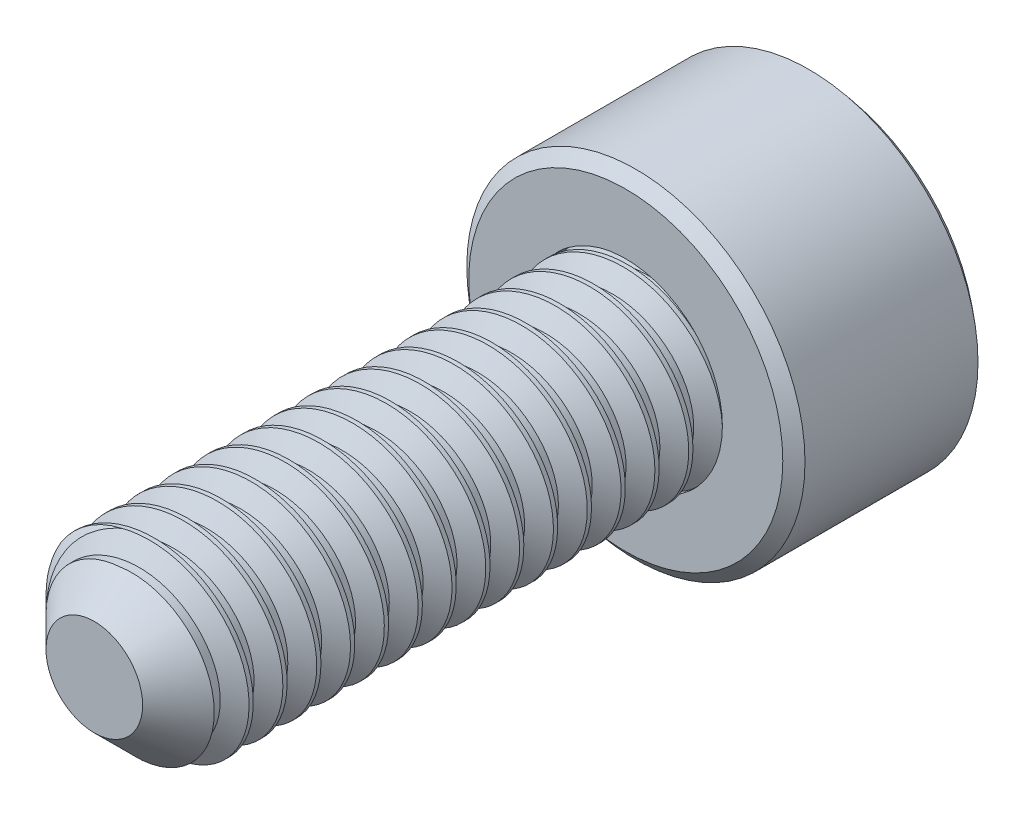
SolidWorks part; units mm, degrees
ref_plane "Front Plane" through (0, 0, 0) normal (0, 0, 1) x (1, 0, 0)
ref_plane "Top Plane" through (0, 0, 0) normal (0, 1, 0) x (1, 0, 0)
ref_plane "Right Plane" through (0, 0, 0) normal (1, 0, 0) x (0, 0, -1)
sketch "Sketch3" plane through (0, 0, 0) normal (0, 0, 1) x (1, 0, 0)
  circle A0 centre (0, 0) radius 2
  dimension "D1" = 4
extrude "Boss-Extrude2" add sketch "Sketch3" along normal blind 11
sketch "Sketch4" plane through (0, 0, 0) normal (0, 0, -1) x (-1, 0, 0)
  circle A0 centre (0, 0) radius 3.5
  dimension "D1" = 7
extrude "Boss-Extrude3" add sketch "Sketch4" along normal blind 4
sketch "Sketch5" plane through (0, 0, -4) normal (0, 0, -1) x (-1, 0, 0)
  circle A0 centre (0, 0) radius 3.25
  dimension "D1" = 6.5
extrude "Cut-Extrude1" cut sketch "Sketch5" against normal blind 4 draft 50 flip side to cut
sketch "Sketch6" plane through (0, 0, 0) normal (0, 0, 1) x (1, 0, 0)
  circle A0 centre (0, 0) radius 3.25
  dimension "D1" = 6.5
extrude "Cut-Extrude2" cut sketch "Sketch6" against normal blind 4 draft 50 flip side to cut
thread "Thread1" pitch 0.7 method cut profile "Thread Profile1" start angle 0, offset 3.3, length 11, pitch 0.7, diameter 4
ref_plane "Plane1" through (2, 0, -0.7) normal (0, -1, 0) x (1, 0, 0)
sketch "Thread Profile1" plane through (2, 0, -0.7) normal (0, -1, 0) x (1, 0, 0)
  line L0 (0, 0) -> (0, 0.7) construction
  line L11 (0, 0) -> (0, 0.6125)
  line L12 (0, 0.6125) -> (-0.3789, 0.3937)
  line L13 (-0.3789, 0.3937) -> (-0.3789, 0.2187)
  line L15 (-0.3789, 0.2187) -> (0, 0)
  line L17 (-0.3789, 0.3062) -> (0, 0.3062) construction
  point P2 (0, 0)
  dimension "Pitch" = 0.7
  dimension "Profile_Angle" = 60
  dimension "Profile_Land" = 0.175
  dimension "Profile_Height" = 0.3789
sketch "Sketch12" plane through (0, 0, -4) normal (0, 0, -1) x (-1, 0, 0)
  line L1 (-0.75, -1.299) -> (0.75, -1.299)
  line L2 (0.75, -1.299) -> (1.5, 0)
  line L3 (1.5, 0) -> (0.75, 1.299)
  line L4 (0.75, 1.299) -> (-0.75, 1.299)
  line L5 (-0.75, 1.299) -> (-1.5, 0)
  line L6 (-1.5, 0) -> (-0.75, -1.299)
  circle A0 centre (0, 0) radius 1.299 construction
  dimension "D1" = 3
extrude "Cut-Extrude3" cut sketch "Sketch12" against normal blind 2.8
fillet "Fillet2" radius 0.1 12 edges at (0.75, 1.299, -2.6) (0, -1.299, -1.2) (1.125, -0.6495, -1.2) (-1.125, -0.6495, -1.2) (-1.125, 0.6495, -1.2) (0, 1.299, -1.2) (1.125, 0.6495, -1.2) (1.5, 0, -2.6) (0.75, -1.299, -2.6) (-1.5, 0, -2.6) (-0.75, -1.299, -2.6) (-0.75, 1.299, -2.6)
fillet "Fillet3" radius 0.1 12 edges at (0.7423, 1.2856, -4) (0, 1.299, -4) (-0.7423, 1.2856, -4) (-1.125, 0.6495, -4) (-1.4845, 0, -4) (-1.125, -0.6495, -4) (-0.7423, -1.2856, -4) (0, -1.299, -4) (0.7423, -1.2856, -4) (1.125, -0.6495, -4) (1.4845, 0, -4) (1.125, 0.6495, -4)
chamfer "Chamfer2" distance 1 angle 45 1 edges at (2, 0, 11)
